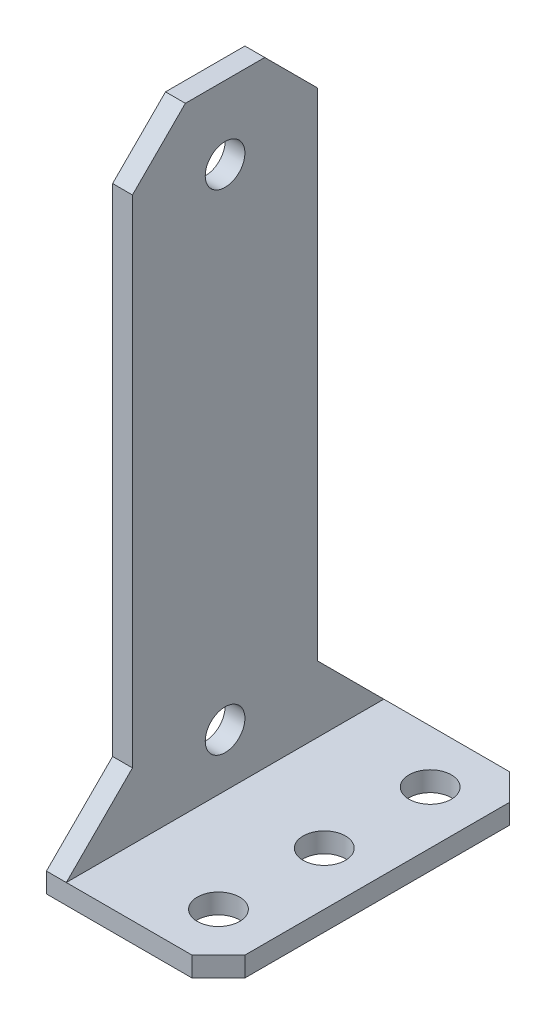
SolidWorks part; units mm, degrees
material "ABS"
ref_plane "Front" through (0, 0, 0) normal (0, 0, 1) x (1, 0, 0)
ref_plane "Top" through (0, 0, 0) normal (0, 1, 0) x (1, 0, 0)
ref_plane "Right" through (0, 0, 0) normal (1, 0, 0) x (0, 0, -1)
sketch "Эскиз1" plane through (0, 0, 0) normal (0, 0, 1) x (1, 0, 0)
  line L0 (0, 0) -> (0, 48)
  line L1 (0, 48) -> (1.5, 48)
  line L2 (1.5, 48) -> (1.5, 1.5)
  line L3 (0, 0) -> (13, 0)
  line L4 (13, 0) -> (13, 1.5)
  line L5 (13, 1.5) -> (1.5, 1.5)
  dimension "D1" = 48
  dimension "D2" = 13
  dimension "D3" = 1.5
  dimension "D4" = 1.5
extrude "Бобышка-Вытянуть1" add sketch "Эскиз1" along normal mid plane 24
sketch "Эскиз2" plane through (0, 1.5, 0) normal (0, 1, 0) x (1, 0, 0)
  line L0 (13, 0) -> (9, 0) construction
  line L1 (13, -12) -> (13, 12) construction
  line L2 (9, 0) -> (9, 6.3835) construction
  line L3 (9, 0) -> (-3.2605, 0) construction
  circle A0 centre (9, 0) radius 1.6
  circle A7 centre (9, 0) radius 8 construction
  circle A8 centre (9, -8) radius 1.6
  circle A9 centre (9, 8) radius 1.6
  dimension "D1" = 4
  dimension "D2" = 3.2
extrude "Вырез-Вытянуть1" cut sketch "Эскиз2" against normal blind 45.2
chamfer "Фаска1" distance 2 angle 45 2 edges at (13, 0.75, -12) (13, 0.75, 12)
sketch "Эскиз4" plane through (0, 0, 0) normal (-1, 0, 0) x (0, 0, 1)
  line L1 (0, 48) -> (0, 0) construction
  line L3 (12, 48) -> (-12, 48) construction
  circle A4 centre (0, 24) radius 18.5 construction
  circle A5 centre (0, 42.5) radius 1.5
  circle A6 centre (0, 5.5) radius 1.5
  point P11 (0, 24)
  dimension "D2" = 37
  dimension "D1" = 24
extrude "Вырез-Вытянуть2" cut sketch "Эскиз4" against normal through all contours A6 | A5 region at (0, 42.5, 0) region at (0, 5.5, 0)
sketch "Эскиз6" plane through (0, 0, 0) normal (-1, 0, 0) x (0, 0, 1)
  line L0 (0, 42.5) -> (7, 42.5)
  line L1 (7, 42.5) -> (33.3884, 42.5)
  line L2 (7, 42.5) -> (7, 72.5)
  line L3 (33.3884, 42.5) -> (33.3884, 72.5)
  line L4 (7, 72.5) -> (33.3884, 72.5)
  line L5 (7, 42.5) -> (7, 1.5)
  line L6 (7, 42.5) -> (33.1795, 42.5)
  line L7 (7, 1.5) -> (33.1795, 1.5)
  line L8 (33.1795, 42.5) -> (33.1795, 1.5)
  line L9 (0, 42.5) -> (0, 54.6433) construction
  line L10 (-33.1795, 42.5) -> (-33.1795, 1.5)
  line L11 (-7, 1.5) -> (-33.1795, 1.5)
  line L12 (-7, 42.5) -> (-33.1795, 42.5)
  line L13 (-7, 42.5) -> (-7, 1.5)
  line L14 (-7, 72.5) -> (-33.3884, 72.5)
  line L15 (-33.3884, 42.5) -> (-33.3884, 72.5)
  line L16 (-7, 42.5) -> (-7, 72.5)
  line L17 (-7, 42.5) -> (-33.3884, 42.5)
  line M7 (-12, 48) -> (-12, 0)
  line M9 (12, 0) -> (12, 48)
  line M11 (12, 48) -> (-12, 48)
  dimension "D1" = 41
  dimension "D2" = 30
extrude "Вырез-Вытянуть3" cut sketch "Эскиз6" against normal blind 10 contours L13 L12 L11 M7 | L12 L16 M11 M7 | L17 L12 L16 L14 L15 M7 M11 | L8 L1 L7 M9 | L5 L7 L1 M9 | L1 L3 L4 L2 region at (0, 22, 22.5898) region at (0, 45.25, -9.5) region at (0, 57.9408, -20.5791) region at (0, 22, 9.5) region at (0, 22, -9.5)
chamfer "Фаска2" distance 4 angle 45 2 edges at (0.75, 48, 7) (0.75, 48, -7)
chamfer "Фаска4" distance 5 angle 45 2 edges at (0.75, 1.5, 7) (0.75, 1.5, -7)
